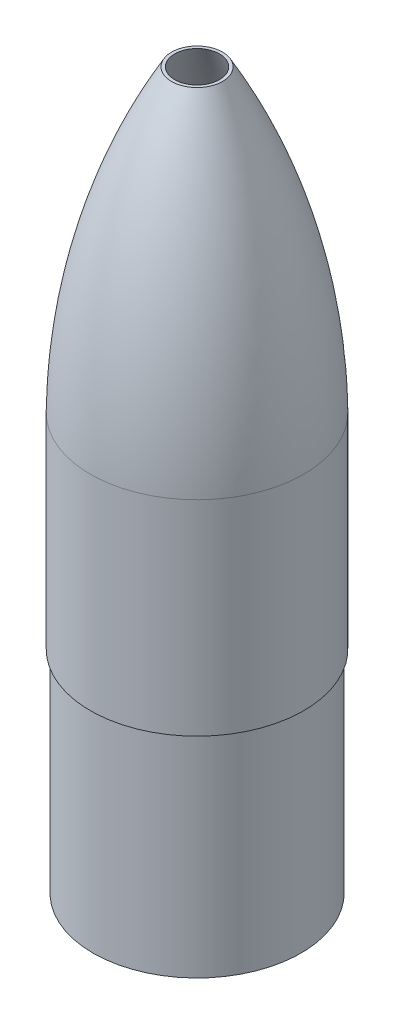
SolidWorks part; units mm, degrees
other "Markup1"
sketch "Sketch4" plane through (78.16, -154.2442, 78.16) normal (0.9651, -0.1718, 0.1975) x (-0.1686, -0.9851, -0.0334)
material "A-Glass Fiber"
ref_plane "Front Plane" through (0, 0, 0) normal (0, 0, 1) x (1, 0, 0)
ref_plane "Top Plane" through (0, 0, 0) normal (0, 1, 0) x (1, 0, 0)
ref_plane "Right Plane" through (0, 0, 0) normal (1, 0, 0) x (0, 0, -1)
sketch "Sketch1" plane through (0, 0, 0) normal (0, 0, 1) x (1, 0, 0)
  line L0 (78.16, 0.5558) -> (78.16, 150.5558)
  line L3 (0, 0) -> (0, 614.1078) construction
  line L6 (0, -198.8179) -> (0, -350.074)
  line L7 (76.2, 0.5558) -> (76.2, 150.5443)
  line L8 (78.16, 0.5558) -> (76.2, 0.5558)
  line L9 (0, 400) -> (0, 396.4892)
  spline S0 degree 4 poles (-15.3468, 421.2955) (-15.0103, 420.856) (-14.3388, 419.9758) (-13.3353, 418.6515) (-12.0074, 416.8814) (-10.6914, 415.1091) (-9.395, 413.3458) (-8.1033, 411.5702) (-6.8448, 409.8242) (-5.5578, 408.0177) (-4.3521, 406.3128) (-3.0104, 404.3884) (-1.9663, 402.8848) (-0.427, 400.6308) (0.2737, 399.5978) (1.5381, 397.7184) (2.5222, 396.2406) (3.5056, 394.7509) (4.501, 393.2308) (5.4828, 391.7179) (6.46, 390.199) (7.4365, 388.6679) (8.4121, 387.1246) (16.4914, 374.2288) (28.348, 353.3444) (42.5411, 323.7528) (57.5292, 282.9984) (68.4498, 242.8729) (74.1096, 210.0768) (76.6559, 184.8086) (77.5185, 170.0675) (77.6804, 166.8514) (77.8002, 164.1053) (77.872, 162.2907) (77.9363, 160.4857) (77.9934, 158.6832) (78.0434, 156.8667) (78.0859, 155.0826) (78.1211, 153.3065) (78.1553, 151.0401) (78.1694, 149.7893) (78.1915, 147.0488) (78.1921, 145.2128) (78.1883, 142.8552) (78.1709, 140.7595) (78.1445, 138.5315) (78.1069, 136.371) (78.059, 134.1662) (78, 131.9694) (77.93, 129.7536) (77.8488, 127.533) (77.7798, 125.8658) (77.7301, 124.7552) (77.7044, 124.2) knots 0 0 0 0 0 0.006969 0.013937 0.020906 0.027875 0.034717 0.04156 0.048403 0.055246 0.062088 0.068931 0.075774 0.082616 0.0883 0.093983 0.099666 0.10535 0.111033 0.116716 0.122399 0.128083 0.133891 0.1397 0.313954 0.430124 0.546294 0.685698 0.836718 0.848335 0.865761 0.871569 0.877253 0.882936 0.888619 0.894302 0.899986 0.905669 0.911352 0.917035 0.923907 0.930779 0.93765 0.944522 0.951393 0.958265 0.965136 0.972008 0.979006 0.986004 0.993002 1 1 1 1 1 construction
  spline S1 degree 4 poles (0, 400) (0.2113, 399.6881) (0.6358, 399.0596) (1.5381, 397.7184) (2.5222, 396.2406) (3.5056, 394.7509) (4.501, 393.2308) (5.4828, 391.7179) (6.46, 390.199) (7.4365, 388.6679) (8.4121, 387.1246) (16.4914, 374.2288) (28.348, 353.3444) (42.5411, 323.7528) (57.5292, 282.9984) (68.4498, 242.8729) (74.1096, 210.0768) (76.6559, 184.8086) (77.5185, 170.0675) (77.6804, 166.8514) (77.8002, 164.1053) (77.872, 162.2907) (77.9363, 160.4857) (77.9934, 158.6832) (78.0434, 156.8667) (78.0859, 155.0826) (78.1211, 153.3065) (78.1455, 151.6911) (78.1556, 150.9325) (78.16, 150.5558) knots 0.082616 0.082616 0.082616 0.082616 0.082616 0.0883 0.093983 0.099666 0.10535 0.111033 0.116716 0.122399 0.128083 0.133891 0.1397 0.313954 0.430124 0.546294 0.685698 0.836718 0.848335 0.865761 0.871569 0.877253 0.882936 0.888619 0.894302 0.899986 0.905669 0.911352 0.917035 0.917035 0.917035 0.917035 0.917035
  spline S2 degree 1 poles (-1.6226, 398.9005) (76.2, 150.5443) knots 0 0 1 1 construction
  spline S3 degree 3 poles (-1.6226, 398.9005) (-1.4527, 398.6498) (-1.1386, 398.1849) (-0.5196, 397.2651) (0.1099, 396.3257) (0.6873, 395.459) (1.2483, 394.6123) (1.9995, 393.4729) (3.323, 391.4513) (5.1827, 388.5671) (9.5921, 381.5907) (18.7945, 366.2671) (36.7943, 332.2032) (57.0765, 280.9241) (69.6847, 227.2404) (74.343, 188.9958) (75.531, 171.161) (75.8913, 162.9157) (76.0101, 159.4861) (76.0769, 157.0706) (76.1102, 155.7062) (76.1328, 154.6907) (76.1533, 153.65) (76.1724, 152.5206) (76.189, 151.4097) (76.1964, 150.8476) (76.2, 150.5443) knots 0.082616 0.082616 0.082616 0.082616 0.085876 0.089135 0.092394 0.095654 0.098913 0.102172 0.108691 0.121728 0.134765 0.186913 0.29121 0.499804 0.708398 0.812695 0.864843 0.877881 0.890918 0.897436 0.900696 0.903955 0.907214 0.910473 0.913733 0.916992 0.916992 0.916992 0.916992 only from (0, 396.4892) to (76.2, 150.5443)
  point P11 (0, 400)
  dimension "D1" = 400
  dimension "D2" = 150
  dimension "D3" = 1.96
  dimension "D4" = 76.2
revolve "Revolve3" add sketch "Sketch1" angle 360 about L6 reverse direction yes
ref_plane "Plane1" through (0, 150.5558, 0) normal (0, 1, 0) x (1, 0, 0)
sketch "Sketch2" plane through (0, 150.5558, 0) normal (0, 1, 0) x (1, 0, 0)
  circle A0 centre (0, 0) radius 76.2 construction
  circle A1 centre (0, 0) radius 76.2
  circle A2 centre (0, 0) radius 73.2
  dimension "D1" = 3
extrude "Boss-Extrude1" add sketch "Sketch2" against normal blind 304.8
ref_plane "Plane2" through (0, 400, 0) normal (0, -1, 0) x (-1, 0, 0)
sketch "Sketch3" plane through (0, 400, 0) normal (0, -1, 0) x (-1, 0, 0)
  circle A0 centre (0, 0) radius 126.4604
extrude "Cut-Extrude1" cut sketch "Sketch3" along normal blind 30 contours A0
